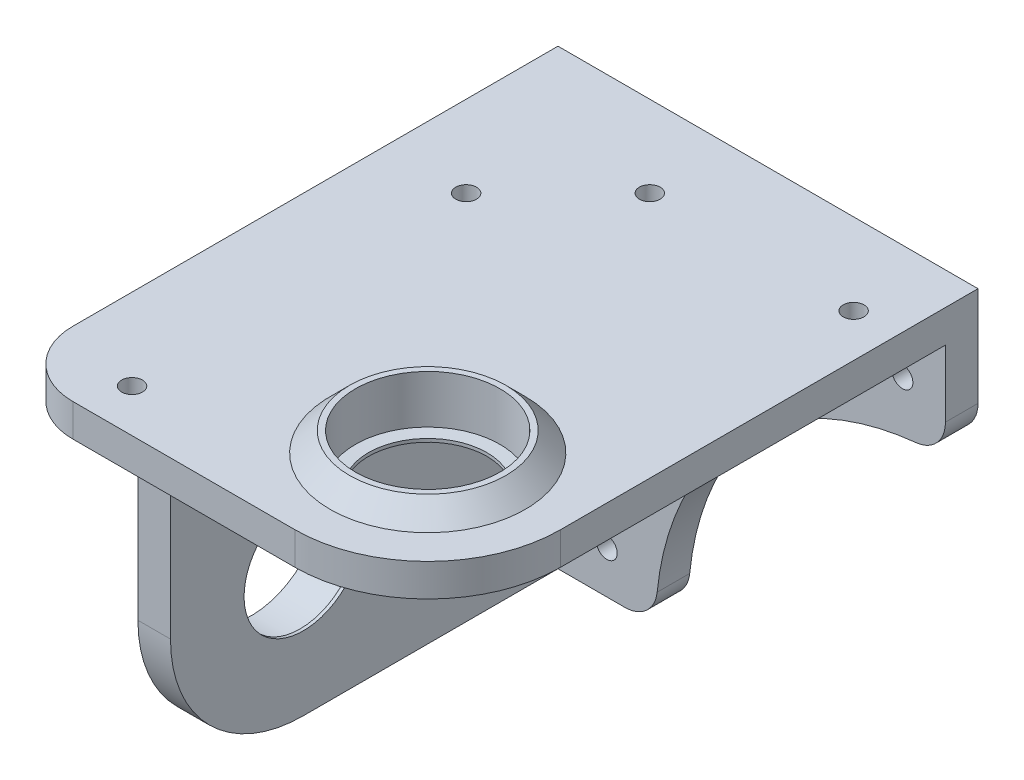
SolidWorks part; units mm, degrees
ref_plane "Front Plane" through (0, 0, 0) normal (0, 0, 1) x (1, 0, 0)
ref_plane "Top Plane" through (0, 0, 0) normal (0, 1, 0) x (1, 0, 0)
ref_plane "Right Plane" through (0, 0, 0) normal (1, 0, 0) x (0, 0, -1)
sketch "Sketch1" plane through (0, 0, 0) normal (0, 0, 1) x (1, 0, 0)
  line L0 (-1060.6916, 12.25) -> (48939.3083, 12.25) construction
  line L1 (-32.25, -32.25) -> (-16.9968, -32.25)
  line L2 (-32.25, -32.25) -> (-32.25, 32.25)
  line L3 (-32.25, 32.25) -> (32.25, 32.25)
  line L4 (32.25, 16.9968) -> (32.25, 32.25)
  line L5 (-32.25, -32.25) -> (32.25, 32.25) construction
  line L6 (-32.25, 32.25) -> (32.25, -32.25) construction
  line L7 (-12.25, -1023.3214) -> (-12.25, 48976.6786) construction
  line L8 (-1048.9078, 19.75) -> (48951.0922, 19.75) construction
  line L9 (-19.75, -955.4396) -> (-19.75, 49044.5604) construction
  arc A0 (27.7551, 12.0224) -> (-12.0224, -27.7551) centre (32.25, -32.25) ccw
  circle A1 centre (-19.75, 19.75) radius 1.6
  circle A2 centre (-5.65, 19.75) radius 1.6
  circle A3 centre (25.65, 19.75) radius 1.6
  circle A4 centre (-19.75, 5.65) radius 1.6
  circle A5 centre (-19.75, -25.65) radius 1.6
  arc A6 (27.7551, 12.0224) -> (32.25, 16.9968) centre (27.25, 16.9968) ccw
  arc A7 (-12.0224, -27.7551) -> (-16.9968, -32.25) centre (-16.9968, -27.25) cw
  point P0 (0, 0)
  point P28 (32.25, 12.25)
  point P31 (-12.25, -32.25)
  dimension "D4" = 7.5
  dimension "D6" = 3.2
  dimension "D8" = 5
  dimension "D9" = 5
  dimension "D10" = 5
  dimension "D11" = 5
  dimension "D1" = 64.5
  dimension "D2" = 20
  dimension "D3" = 20
  dimension "D5" = 7.5
  dimension "D7" = 5
extrude "Boss-Extrude1" add sketch "Sketch1" along normal blind 5
sketch "Sketch2" plane through (0, 0, 5) normal (0, 0, 1) x (1, 0, 0)
  line L0 (32.25, 16.9968) -> (32.25, 32.25) construction
  line L1 (-32.25, 32.25) -> (32.25, 32.25)
  line L2 (-32.25, 32.25) -> (-32.25, 27.25)
  line L3 (-27.25, 27.25) -> (32.25, 27.25)
  line L4 (32.25, 32.25) -> (32.25, 27.25)
  line L5 (-32.25, -32.25) -> (-16.9968, -32.25) construction
  line L7 (-32.25, 27.25) -> (-32.25, -32.25)
  line L8 (-32.25, -32.25) -> (-27.25, -32.25)
  line L9 (-27.25, 27.25) -> (-27.25, -32.25)
  dimension "D1" = 5
extrude "Boss-Extrude2" add sketch "Sketch2" along normal blind 79.5
sketch "Sketch3" plane through (0, 32.25, 0) normal (0, 1, 0) x (1, 0, 0)
  line L2 (32.25, -84.5) -> (-32.25, -84.5) construction
  line L3 (32.25, -84.5) -> (32.25, 0) construction
  line L4 (11.85, -84.5) -> (11.85, -91.4766)
  line L5 (11.85, -91.4766) -> (44.1004, -91.4766)
  line L6 (44.1004, -91.4766) -> (44.1004, -64.1)
  line L7 (44.1004, -64.1) -> (32.25, -64.1)
  circle A0 centre (11.85, -64.1) radius 15 construction
  arc A1 (11.85, -84.5) -> (32.25, -64.1) centre (11.85, -64.1) ccw
  circle A2 centre (11.85, -64.1) radius 11.1
  dimension "D1" = 30
  dimension "D2" = 5.4
  dimension "D3" = 22.2
extrude "Cut-Extrude1" cut sketch "Sketch3" against normal through all
sketch "Sketch4" plane through (0, 32.25, 0) normal (0, 1, 0) x (1, 0, 0)
  circle A0 centre (11.85, -64.1) radius 15
  circle A1 centre (11.85, -64.1) radius 15 construction
  circle A2 centre (11.85, -64.1) radius 11.1
  circle A3 centre (11.85, -64.1) radius 11.1 construction
extrude "Boss-Extrude3" add sketch "Sketch4" along normal blind 3
chamfer "Chamfer1" distance 3 angle 45 1 edges at (11.85, 35.25, 79.1)
sketch "Sketch5" plane through (0, 27.25, 0) normal (0, -1, 0) x (1, 0, 0)
  circle A0 centre (11.85, 64.1) radius 11.1
  circle A1 centre (11.85, 64.1) radius 9.1
  circle A2 centre (11.85, 64.1) radius 11.1 construction
  dimension "D1" = 2
extrude "Boss-Extrude4" add sketch "Sketch5" against normal blind 1
chamfer "Chamfer2" distance 0.5 distance2 10 1 edges at (11.85, 28.25, 55) first distance on face at (11.85, 28.25, 55)
sketch "Sketch6" plane through (0, 32.25, 0) normal (0, 1, 0) x (1, 0, 0)
  line L0 (-1014.3468, -12.5) -> (48985.6532, -12.5) construction
  line L1 (-19.75, -1047.3352) -> (-19.75, 48952.6648) construction
  line L2 (32.25, 0) -> (-32.25, 0) construction
  line L3 (-32.25, -84.5) -> (-32.25, 0) construction
  line L4 (-1001.8593, -20) -> (48998.1407, -20) construction
  line L5 (-12.25, -974.0532) -> (-12.25, 49025.9468) construction
  line L9 (11.85, -84.5) -> (-32.25, -84.5) construction
  circle A0 centre (-19.75, -26.6) radius 1.6
  circle A1 centre (-19.75, -77.9) radius 1.6
  circle A2 centre (-5.65, -12.5) radius 1.6
  circle A3 centre (25.65, -12.5) radius 1.6
  dimension "D5" = 3.2
  dimension "D6" = 5
  dimension "D7" = 5
  dimension "D1" = 12.5
  dimension "D2" = 12.5
  dimension "D3" = 7.5
  dimension "D4" = 7.5
extrude "Cut-Extrude2" cut sketch "Sketch6" against normal through all
sketch "Sketch7" plane through (-32.25, 0, 0) normal (-1, 0, 0) x (0, 0, 1)
  line L0 (64.5, 19.75) -> (64.5, -11.85)
  line L1 (84.5, -32.25) -> (0, -32.25) construction
  line L2 (0, 32.25) -> (0, -32.25) construction
  line L3 (72, 27.25) -> (84.5, 27.25)
  line L4 (84.5, 27.25) -> (84.5, -32.25)
  line L5 (44.1, -32.25) -> (84.5, -32.25)
  line L6 (84.5, 32.25) -> (84.5, -32.25) construction
  line L7 (84.5, 32.25) -> (0, 32.25) construction
  line L8 (-984.8674, 19.75) -> (49015.1326, 19.75) construction
  line L9 (-988.0043, 12.25) -> (49011.9957, 12.25) construction
  line L10 (12.5, -945.2547) -> (12.5, 49054.7453) construction
  line L11 (20, -945.3003) -> (20, 49054.6997) construction
  line L12 (0, -201023.3214) -> (0, 248976.6786) construction
  circle A0 centre (44.1, -11.85) radius 15 construction
  circle A1 centre (44.1, -11.85) radius 11.1
  arc A2 (64.5, -11.85) -> (44.1, -32.25) centre (44.1, -11.85) cw
  arc A3 (64.5, 19.75) -> (72, 27.25) centre (72, 19.75) cw
  circle A4 centre (57.9, 19.75) radius 1.6
  circle A5 centre (26.6, 19.75) radius 1.6
  circle A6 centre (12.5, 5.65) radius 1.6
  circle A7 centre (12.5, -25.65) radius 1.6
  dimension "D3" = 30
  dimension "D6" = 22.2
  dimension "D11" = 7.5
  dimension "D12" = 3.2
  dimension "D14" = 5
  dimension "D16" = 5
  dimension "D1" = 64.5
  dimension "D2" = 5
  dimension "D4" = 5.4
  dimension "D5" = 5.4
  dimension "D7" = 12.5
  dimension "D8" = 7.5
  dimension "D9" = 12.5
  dimension "D10" = 7.5
  dimension "D13" = 5
  dimension "D15" = 5
extrude "Cut-Extrude3" cut sketch "Sketch7" against normal through all
sketch "Sketch8" plane through (-27.25, 0, 0) normal (1, 0, 0) x (0, 0, -1)
  circle A0 centre (-44.1, -11.85) radius 9.1
  circle A1 centre (-44.1, -11.85) radius 11.1 construction
  circle A2 centre (-44.1, -11.85) radius 11.1
  dimension "D1" = 2
extrude "Boss-Extrude5" add sketch "Sketch8" against normal blind 1
chamfer "Chamfer3" distance 0.5 distance2 10 1 edges at (-28.25, -2.75, 44.1) first distance on face at (-28.25, -2.75, 44.1)
sketch "Sketch9" plane through (-32.25, 0, 0) normal (-1, 0, 0) x (0, 0, 1)
  circle A0 centre (44.1, -11.85) radius 15
  circle A1 centre (44.1, -11.85) radius 15 construction
  circle A2 centre (44.1, -11.85) radius 11.1
  circle A3 centre (44.1, -11.85) radius 11.1 construction
extrude "Boss-Extrude6" add sketch "Sketch9" along normal blind 3
chamfer "Chamfer4" distance 3 angle 45 1 edges at (-35.25, -11.85, 59.1)
fillet "Fillet1" radius 10 1 edges at (-32.25, 29.75, 84.5)
